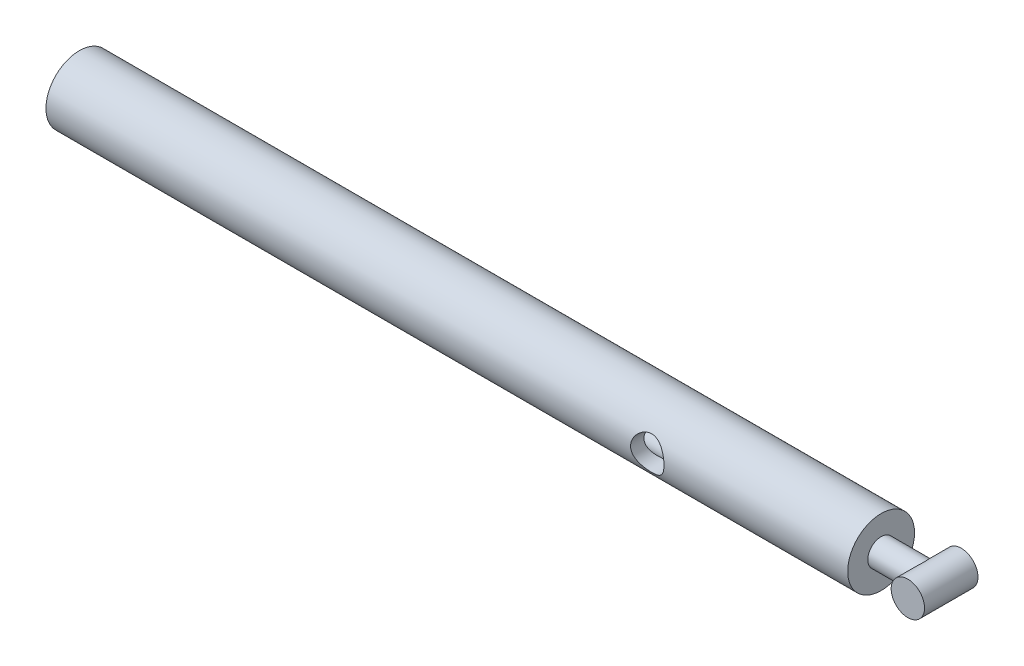
SolidWorks part; units mm, degrees
ref_plane "Front Plane" through (0, 0, 0) normal (0, 0, 1) x (1, 0, 0)
ref_plane "Top Plane" through (0, 0, 0) normal (0, 1, 0) x (1, 0, 0)
ref_plane "Right Plane" through (0, 0, 0) normal (1, 0, 0) x (0, 0, -1)
sketch "Sketch1" plane through (0, 0, 0) normal (1, 0, 0) x (0, 0, -1)
  circle A0 centre (0, 0) radius 5
  dimension "D1" = 10
extrude "Boss-Extrude1" add sketch "Sketch1" against normal blind 120
sketch "Sketch2" plane through (-120, 0, 0) normal (-1, 0, 0) x (0, 0, 1)
  circle A0 centre (0, 0) radius 2.5
  dimension "D1" = 5
extrude "Cut-Extrude1" cut sketch "Sketch2" against normal blind 20
sketch "Sketch3" plane through (-100, 0, 0) normal (-1, 0, 0) x (0, 0, 1)
  circle A0 centre (0, 0) radius 3
  dimension "D1" = 6
extrude "Cut-Extrude2" cut sketch "Sketch3" against normal blind 80
sketch "Sketch4" plane through (0, 0, 0) normal (1, 0, 0) x (0, 0, -1)
  circle A0 centre (0, 0) radius 2
  dimension "D1" = 4
extrude "Boss-Extrude2" add sketch "Sketch4" along normal blind 8
sketch "Sketch5" plane through (0, 0, 0) normal (0, 0, 1) x (1, 0, 0)
  line L0 (8, -2) -> (8, 2) construction
  circle A0 centre (8, 0) radius 2.5
  dimension "D1" = 5
extrude "Boss-Extrude3" add sketch "Sketch5" along normal blind 4 and the other way blind 4
sketch "Sketch6" plane through (0, 0, 0) normal (0, 0, 1) x (1, 0, 0)
  circle A0 centre (-30, 0) radius 2.5
  dimension "D1" = 5
  dimension "D2" = 30
extrude "Cut-Extrude3" cut sketch "Sketch6" against normal through all and the other way through all
sketch3d "3DSketch2"
  line L0 (-120, 2.5, 0) -> (-115, 2.5, 0) construction
  circle A0 centre (-120, 0, 0) radius 2.5 construction
  point P4 (-122.5, 0, 0)
  dimension "D1" = 2.5
  dimension "D2" = 5
